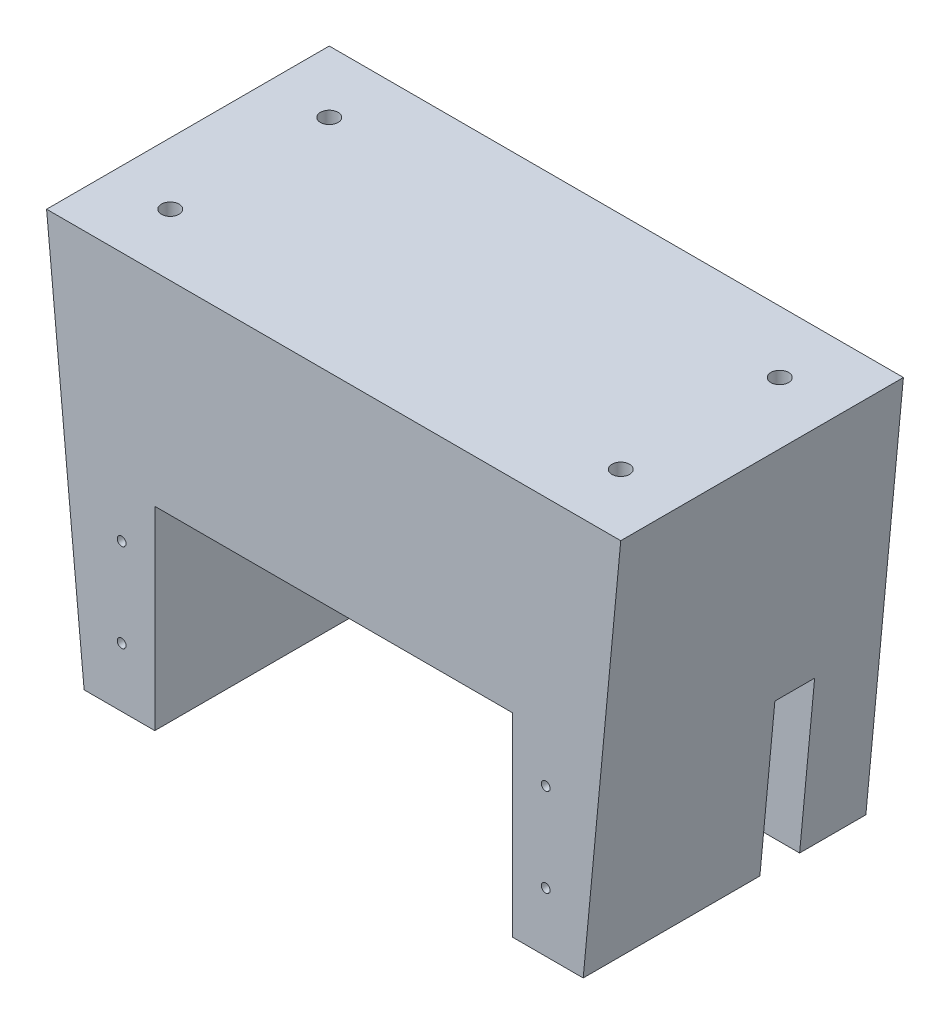
SolidWorks part; units mm, degrees
ref_plane "Plano frontal" through (0, 0, 0) normal (0, 0, 1) x (1, 0, 0)
ref_plane "Plano superior" through (0, 0, 0) normal (0, 1, 0) x (1, 0, 0)
ref_plane "Plano direito" through (0, 0, 0) normal (1, 0, 0) x (0, 0, -1)
sketch "Esboço1" plane through (0, 0, 0) normal (0, 0, 1) x (1, 0, 0)
  line L0 (-32.5, 31.3195) -> (32.5, 31.3195)
  line L1 (32.5, 31.3195) -> (28.25, -13.6805)
  line L2 (28.25, -13.6805) -> (20.25, -13.6805)
  line L3 (20.25, -13.6805) -> (20.25, 8.3195)
  line L4 (20.25, 8.3195) -> (-20.25, 8.3195)
  line L5 (-20.25, 8.3195) -> (-20.25, -13.6805)
  line L6 (-20.25, -13.6805) -> (-28.25, -13.6805)
  line L7 (-28.25, -13.6805) -> (-32.5, 31.3195)
  point P6 (0, 8.3195)
  point P9 (0, 31.3195)
  dimension "D1" = 40.5
  dimension "D2" = 22
  dimension "D3" = 8
  dimension "D4" = 8
  dimension "D5" = 65
  dimension "D6" = 22
  dimension "D7" = 45
extrude "Ressalto-extrusão1" add sketch "Esboço1" along normal blind 30
ref_plane "Plano1" through (40, 0, 0) normal (1, 0, 0) x (0, 0, -1)
sketch "Esboço3" plane through (40, 0, 0) normal (1, 0, 0) x (0, 0, -1)
  line L0 (-10, -13.6805) -> (-10, 4.3195)
  line L1 (-30, -13.6805) -> (0, -13.6805) construction
  line L2 (-10, 4.3195) -> (-5.5, 4.3195)
  line L3 (-5.5, 4.3195) -> (-5.5, -13.6805)
  line L4 (-30, -13.6805) -> (-30, 31.3195) construction
  line L5 (-10, -13.6805) -> (-5.5, -13.6805)
  dimension "D1" = 20
  dimension "D2" = 18
  dimension "D3" = 4.5
extrude "Corte-extrusão2" cut sketch "Esboço3" against normal blind 28.5
sketch "Esboço4" plane through (0, 0, 0) normal (0, 0, -1) x (-1, 0, 0)
  line L0 (-32.5, 31.3195) -> (32.5, 31.3195)
  line L1 (32.5, 31.3195) -> (28.25, -13.6805)
  line L2 (28.25, -13.6805) -> (20.25, -13.6805)
  line L6 (-20.25, -13.6805) -> (-28.25, -13.6805)
  line L7 (-28.25, -13.6805) -> (-32.5, 31.3195)
  line L8 (-20.25, -13.6805) -> (20.25, -13.6805)
extrude "Ressalto-extrusão2" add sketch "Esboço4" along normal blind 2
sketch "Esboço5" plane through (0, 0, 30) normal (0, 0, 1) x (1, 0, 0)
  line L0 (-24, 3.0195) -> (24, 3.0195) construction
  line L1 (-20.25, 8.3195) -> (20.25, 8.3195) construction
  circle A0 centre (-24, 3.0195) radius 0.5
  circle A1 centre (24, 3.0195) radius 0.5
  circle A2 centre (-24, -6.9805) radius 0.5
  circle A3 centre (24, -6.9805) radius 0.5
  point P6 (0, 8.3195)
  point P7 (0, 3.0195)
  point P12 (0, 0)
  point P13 (0, 0)
  dimension "D1" = 48
  dimension "D2" = 10
  dimension "D4" = 1
  dimension "D5" = 1
  dimension "D6" = 1
  dimension "D7" = 1
  dimension "D3" = 10
  dimension "D8" = 5.3
extrude "Corte-extrusão3" cut sketch "Esboço5" against normal blind 10
sketch "Esboço6" plane through (0, 31.3195, 0) normal (0, 1, 0) x (1, 0, 0)
  line L0 (-32.5, 2) -> (32.5, 2) construction
  line L1 (-32.5, -30) -> (-32.5, 2) construction
  line L2 (32.5, -30) -> (-32.5, -30) construction
  line L3 (32.5, -30) -> (32.5, 2) construction
  circle A0 centre (-25.5, -5) radius 1
  circle A1 centre (-25.5, -23) radius 1
  circle A2 centre (25.5, -5) radius 1
  circle A3 centre (25.5, -23) radius 1
  point P6 (-23.5933, -6.7316)
  dimension "D1" = 7
  dimension "D3" = 2
  dimension "D6" = 2
  dimension "D11" = 2
  dimension "D12" = 2
  dimension "D2" = 7
  dimension "D4" = 7
  dimension "D5" = 7
  dimension "D7" = 7
  dimension "D8" = 7
  dimension "D9" = 7
  dimension "D10" = 7
extrude "Corte-extrusão4" cut sketch "Esboço6" against normal blind 10
